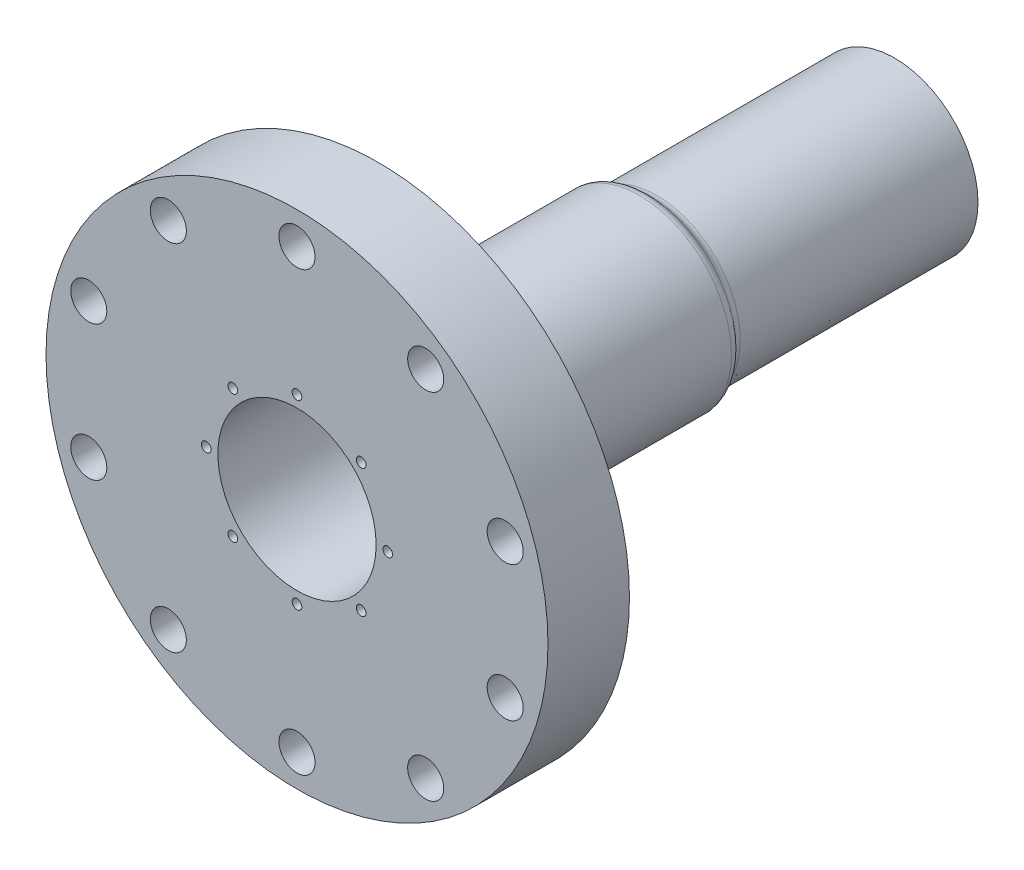
SolidWorks part; units mm, degrees
ref_plane "Front Plane" through (0, 0, 0) normal (0, 0, 1) x (1, 0, 0)
ref_plane "Top Plane" through (0, 0, 0) normal (0, 1, 0) x (1, 0, 0)
ref_plane "Right Plane" through (0, 0, 0) normal (1, 0, 0) x (0, 0, -1)
sketch "Sketch1" plane through (0, 0, 0) normal (0, 0, 1) x (1, 0, 0)
  circle A0 centre (0, 0) radius 18.5
  circle A1 centre (0, 0) radius 19.5
  dimension "D1" = 37
  dimension "D2" = 39
extrude "Extrude1" add sketch "Sketch1" against normal blind 139.7
sketch "Sketch4" plane through (0, 0, 0) normal (0, 0, 1) x (1, 0, 0)
  circle A0 centre (0, 0) radius 19.5
  circle A1 centre (0, 0) radius 58.674
  dimension "D1" = 117.348
extrude "Extrude2" add sketch "Sketch4" against normal blind 19.05
sketch "Sketch5" plane through (0, 0, 0) normal (0, 0, 1) x (1, 0, 0)
  circle A0 centre (0, 51.181) radius 4.2164
  dimension "D1" = 8.4328
  dimension "D2" = 51.181
extrude "Cut-Extrude1" cut sketch "Sketch5" against normal up to next
pattern_circular "CirPattern1" count 10 over 360 about axis through (0, 0, -139.7) along (0, 0, 1) of "Cut-Extrude1"
sketch "Sketch6" plane through (0, 0, 0) normal (0, 0, 1) x (1, 0, 0)
  line L0 (0, 0) -> (0, -32.2747) construction
  line L1 (0, 0) -> (34.1161, 0) construction
  point P4 (15, -15)
  point P5 (-15, -15)
  point P6 (-15, 15)
  point P7 (15, 15)
  dimension "D1" = 30
  dimension "D2" = 30
hole_wizard "#4-40 Tapped Hole2" positions "Sketch9" profile "Sketch8" tap size "#4-40" standard "Ansi Inch"
sketch "Sketch9" plane through (0, 0, 0) normal (0, 0, 1) x (1, 0, 0)
  line L0 (0, 0) -> (34.1161, 0) construction
  line L1 (0, 0) -> (0, -32.2747) construction
  line L2 (0, 21.2132) -> (-21.2132, 0) construction
  line L3 (-21.2132, 0) -> (0, -21.2132) construction
  point P1 (15, -15)
  point P4 (-15, -15)
  point P7 (-15, 15)
  point P10 (15, 15)
  point P13 (0, 21.2132)
  point P15 (-21.2132, 0)
  point P17 (21.2132, 0)
  point P21 (0, -21.2132)
  dimension "D1" = 30
  dimension "D2" = 30
  dimension "D3" = 30
  dimension "D4" = 30
  dimension "D5" = 30
  dimension "D6" = 30
  dimension "D7" = 90
sketch "Sketch8" plane through (15, -15, 0) normal (1, 0, 0) x (0, -1, 0)
  line L0 (0, 0) -> (0, 8.2992)
  line L1 (0, 8.2992) -> (1.1303, 7.62)
  line L2 (1.1303, 7.62) -> (1.1303, 0)
  line L5 (1.1303, 0) -> (0, 0)
  line L10 (0, 8.2992) -> (-1.1303, 7.62) construction
  line L11 (0, -6.35) -> (0, 107.95) construction
  dimension "Tap Drill Dia." = 2.2606
  dimension "Tap Drill Depth" = 7.62
  dimension "Drill Angle" = 118
cosmetic thread "Hole Thread5" parameters "D1"=5.588, "D2"=2.8448
cosmetic thread "Hole Thread6" parameters "D1"=5.588, "D2"=2.8448
cosmetic thread "Hole Thread7" parameters "D1"=5.588, "D2"=2.8448
cosmetic thread "Hole Thread8" parameters "D1"=5.588, "D2"=2.8448
cosmetic thread "Hole Thread9" parameters "D1"=5.588, "D2"=2.8448
cosmetic thread "Hole Thread10" parameters "D1"=5.588, "D2"=2.8448
cosmetic thread "Hole Thread11" parameters "D1"=5.588, "D2"=2.8448
cosmetic thread "Hole Thread12" parameters "D1"=5.588, "D2"=2.8448
sketch "Sketch10" plane through (0, 0, -139.7) normal (0, 0, -1) x (-1, 0, 0)
  circle A0 centre (0, 0) radius 19
  circle A1 centre (0, 0) radius 19.5 construction
  dimension "D1" = 0.5
extrude "Extrude3" cut sketch "Sketch10" against normal blind 25.4
sketch "Sketch11" plane through (0, 0, 0) normal (0, 1, 0) x (1, 0, 0)
  line L0 (0, 123.4369) -> (0, 146.5982) construction
  line L1 (-15, 139.7) -> (-15, 139.2)
  line L3 (19, 139.7) -> (-19, 139.7) construction
  line L4 (-15, 139.2) -> (-16.4406, 139.2)
  line L5 (-16.4406, 139.2) -> (-18.75, 135.2)
  line L6 (-18.75, 135.2) -> (-18.75, 130.3204)
  line L7 (-18.75, 130.3204) -> (-19.25, 130.3204)
  line L8 (-19.25, 130.3204) -> (-19.25, 135.334)
  line L9 (-19.25, 135.334) -> (-16.7293, 139.7)
  line L10 (-16.7293, 139.7) -> (-15, 139.7)
  line L11 (-19.5, 136.2341) -> (-19.5, 130.3204) construction
  dimension "D1" = 0.5
  dimension "D2" = 0.5
  dimension "D3" = 30
  dimension "D4" = 60
  dimension "D5" = 0.5
  dimension "D6" = 4
  dimension "D7" = 19.5
  dimension "D8" = 0.5
revolve "Revolve1" add sketch "Sketch11" angle 360 about L0
sketch "Sketch12" plane through (0, 0, -19.05) normal (0, 0, -1) x (-1, 0, 0)
  circle A0 centre (0, 0) radius 21.5
  circle A1 centre (0, 0) radius 19
  dimension "D1" = 43
extrude "Extrude4" add sketch "Sketch12" along normal blind 63.5
fillet "Fillet1" radius 2.54 1 edges at (-21.5, 0, -82.55)
fillet "Fillet2" radius 2.54 1 edges at (-19.5, 0, -82.55)
